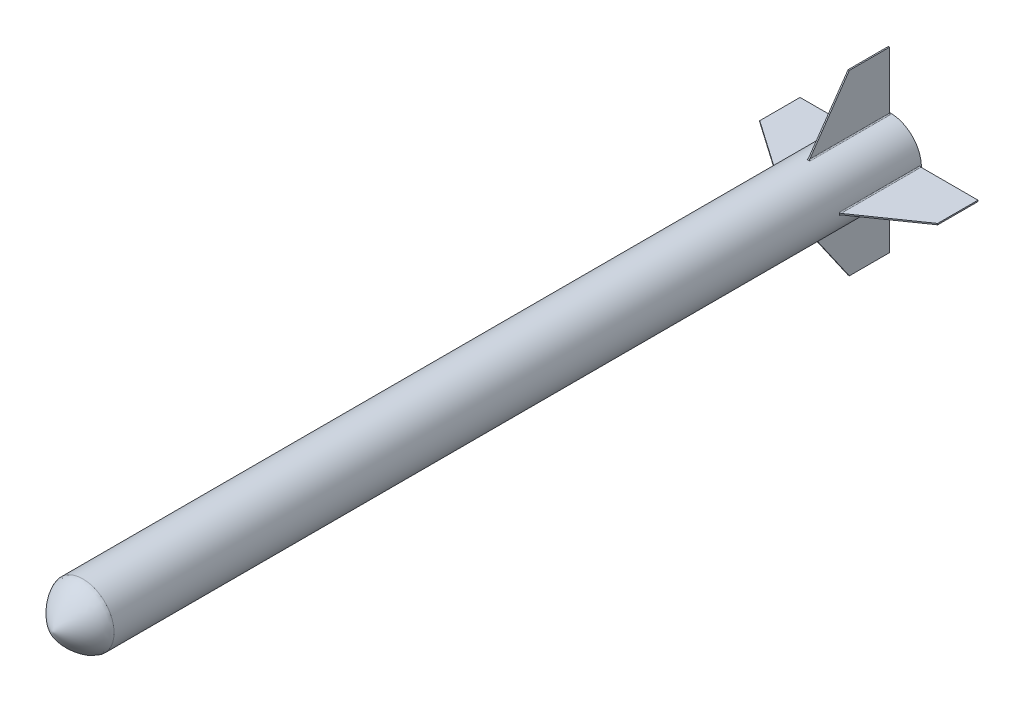
SolidWorks part; units mm, degrees
ref_plane "Front Plane" through (0, 0, 0) normal (0, 0, 1) x (1, 0, 0)
ref_plane "Top Plane" through (0, 0, 0) normal (0, 1, 0) x (1, 0, 0)
ref_plane "Right Plane" through (0, 0, 0) normal (1, 0, 0) x (0, 0, -1)
sketch "Sketch2" plane through (0, 0, 0) normal (1, 0, 0) x (0, 0, -1)
  line L0 (76.2, 78.3229) -> (2111.6925, 78.3229)
  line L1 (2111.6925, 78.3229) -> (2111.6925, 0)
  line L2 (2111.6925, 0) -> (0, 0)
  line L3 (0, 0) -> (-76.2, 0) construction
  line L4 (0, 0) -> (1.2733, 78.3229) construction
  spline S0 degree 4 poles (0, 0) (0.0016, 0.0311) (0.006, 0.0932) (0.0197, 0.217) (0.0562, 0.4716) (0.1202, 0.8246) (0.2899, 1.6076) (0.6817, 3.0445) (1.3694, 5.0886) (2.6636, 8.3284) (4.6272, 12.5048) (7.2216, 17.3138) (10.4785, 22.6637) (14.0485, 27.9719) (17.8301, 33.1312) (21.8031, 38.1444) (25.9547, 43.0106) (30.2773, 47.7255) (34.7673, 52.2815) (39.4246, 56.6664) (44.2526, 60.863) (49.2585, 64.8464) (54.3793, 68.5268) (59.0258, 71.4831) (63.1374, 73.7751) (66.6205, 75.4591) (69.2911, 76.5769) (71.6526, 77.399) (73.5455, 77.9173) (74.7905, 78.1703) (75.5897, 78.2817) (75.9903, 78.3149) (76.13, 78.3218) (76.2, 78.3229) knots 0 0 0 0 0 0.001101 0.002203 0.004406 0.009096 0.013787 0.03054 0.057061 0.085339 0.13714 0.193697 0.250253 0.306809 0.363365 0.419922 0.476478 0.533035 0.589591 0.646147 0.702704 0.75926 0.815816 0.86912 0.897398 0.925676 0.95262 0.971472 0.985786 0.995051 0.997525 1 1 1 1 1 construction
  spline S1 degree 4 poles (0, 0) (0.0016, 0.0311) (0.006, 0.0932) (0.0197, 0.217) (0.0562, 0.4716) (0.1202, 0.8246) (0.2899, 1.6076) (0.6817, 3.0445) (1.3694, 5.0886) (2.6636, 8.3284) (4.6272, 12.5048) (7.2216, 17.3138) (10.4785, 22.6637) (14.0485, 27.9719) (17.8301, 33.1312) (21.8031, 38.1444) (25.9547, 43.0106) (30.2773, 47.7255) (34.7673, 52.2815) (39.4246, 56.6664) (44.2526, 60.863) (49.2585, 64.8464) (54.3793, 68.5268) (59.0258, 71.4831) (63.1374, 73.7751) (66.6205, 75.4591) (69.2911, 76.5769) (71.6526, 77.399) (73.5455, 77.9173) (74.7905, 78.1703) (75.5897, 78.2817) (75.9903, 78.3149) (76.13, 78.3218) (76.2, 78.3229) knots 0 0 0 0 0 0.001101 0.002203 0.004406 0.009096 0.013787 0.03054 0.057061 0.085339 0.13714 0.193697 0.250253 0.306809 0.363365 0.419922 0.476478 0.533035 0.589591 0.646147 0.702704 0.75926 0.815816 0.86912 0.897398 0.925676 0.95262 0.971472 0.985786 0.995051 0.997525 1 1 1 1 1
  dimension "D1" = 2035.4925
  dimension "D2" = 76.2
  dimension "D3" = 78.3229
  dimension "D4" = 78.3229
revolve "Revolve1" add sketch "Sketch2" angle 360 about L2
sketch "Sketch3" plane through (0, 0, -2111.6925) normal (0, 0, -1) x (-1, 0, 0)
  circle A0 centre (0, 0) radius 43.942
  dimension "D1" = 87.884
extrude "Boss-Extrude1" add sketch "Sketch3" along normal blind 15.24
ref_plane "Plane1" through (0, 254, 0) normal (0, 1, 0) x (1, 0, 0)
sketch "Sketch4" plane through (0, 254, 0) normal (0, 1, 0) x (1, 0, 0)
  line L1 (-1.5875, 1905.3175) -> (1.5875, 1905.3175)
  line L2 (-1.5875, 1905.3175) -> (-1.5875, 2108.5175)
  line L3 (-1.5875, 2108.5175) -> (1.5875, 2108.5175)
  line L4 (1.5875, 1905.3175) -> (1.5875, 2108.5175)
  line L5 (78.3229, 2111.6925) -> (-78.3229, 2111.6925) construction
  point P6 (0, 2108.5175)
  dimension "D1" = 3.175
  dimension "D2" = 3.175
  dimension "D3" = 203.2
extrude "Boss-Extrude2" add sketch "Sketch4" against normal up to surface (175.6932 mm away) up to face at (-78.3229, 0, -76.2)
sketch "Sketch5" plane through (-1.5875, 0, 0) normal (-1, 0, 0) x (0, 0, 1)
  line L0 (-2108.5175, 224.3568) -> (-2006.9175, 224.3568)
  line L1 (-2108.5175, 78.3068) -> (-2108.5175, 254) construction
  line L2 (-2006.9175, 224.3568) -> (-1905.3175, 78.3068)
  line L3 (-1905.3175, 78.3068) -> (-1905.3175, 254)
  line L4 (-1905.3175, 254) -> (-2108.5175, 254)
  line L5 (-2108.5175, 254) -> (-2108.5175, 224.3568)
  dimension "D1" = 101.6
  dimension "D2" = 146.05
extrude "Cut-Extrude1" cut sketch "Sketch5" against normal up to next
fillet "Fillet1" radius 2.54 2 edges at (1.5875, 78.3068, -2006.9175) (-1.5875, 78.3068, -2006.9175)
pattern_circular "CirPattern1" count 4 over 360 about axis through (0, 0, -2111.6925) along (0, 0, -1) of "Cut-Extrude1", "Fillet1", "Boss-Extrude2"
equation "\"Body Tube Length\"= 80.1375"
equation "\"D1@Sketch2\"=\"Body Tube Length\""
equation "\"Retainer Diameter\"= 3.46"
equation "\"D1@Sketch3\"=\"Retainer Diameter\""
equation "\"Retainer Height\"= 0.6"
equation "\"D1@Boss-Extrude1\"=\"Retainer Height\""
equation "\"Fin Offset\"= .125"
equation "\"D1@Sketch4\"=\"Fin Offset\""
equation "\"Fin Thickness\"= .125"
equation "\"D2@Sketch4\"=\"Fin Thickness\""
equation "\"Fin Root Chord\"= 8"
equation "\"D3@Sketch4\"=\"Fin Root Chord\""
equation "\"Fin Tip Chord\"= 4"
equation "\"D1@Sketch5\"=\"Fin Tip Chord\""
equation "\"Fin Height\"= 5.75"
equation "\"D2@Sketch5\"=\"Fin Height\""
equation "\"Fin Epoxy Fillet Radius\"=0.1"
equation "\"D1@Fillet1\"=\"Fin Epoxy Fillet Radius\""
equation "\"Nosecone Length\"= 3"
equation "\"D2@Sketch2\"=\"Nosecone Length\""
equation "\"Rocket Radius\"=3.08358"
equation "\"D3@Sketch2\"= \"Rocket Radius\""
equation "\"D4@Sketch2\"=\"Rocket Radius\""
